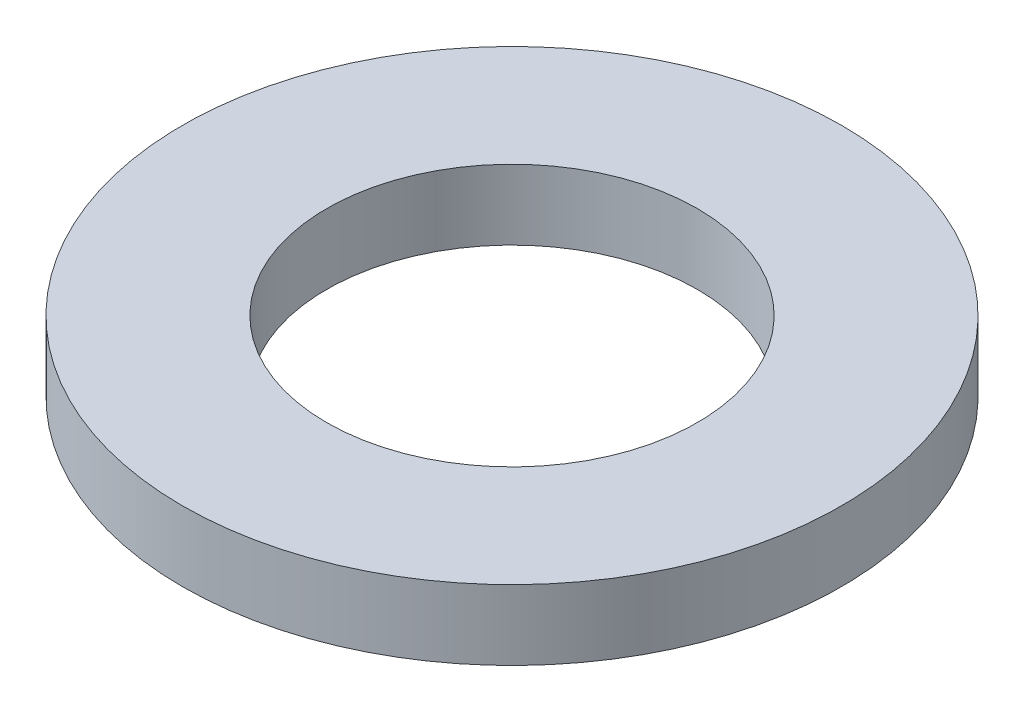
SolidWorks part; units mm, degrees
ref_plane "Front Plane" through (0, 0, 0) normal (0, 0, 1) x (1, 0, 0)
ref_plane "Top Plane" through (0, 0, 0) normal (0, 1, 0) x (1, 0, 0)
ref_plane "Right Plane" through (0, 0, 0) normal (1, 0, 0) x (0, 0, -1)
sketch "Sketch1" plane through (0, 0, 0) normal (0, 1, 0) x (1, 0, 0)
  circle A0 centre (0, 0) radius 80
  dimension "FLANGE_OD" = 160
extrude "Boss-Extrude1" add sketch "Sketch1" along normal blind 17
sketch "Sketch2" plane through (0, 0, 0) normal (0, 1, 0) x (1, 0, 0)
  circle A0 centre (0, 0) radius 45
  dimension "BORE_D" = 90
extrude "Cut-Extrude1" cut sketch "Sketch2" along normal through all
sketch "Sketch3" plane through (0, 17, 0) normal (0, 1, 0) x (1, 0, 0)
  circle A0 centre (0, 0) radius 26.8071 construction
  circle A1 centre (-26.8071, 0) radius 5.8758
  dimension "BOLT_D" = 11.7515
  dimension "BOLT_PCD" = 53.6142
extrude "Cut-Extrude2" cut sketch "Sketch3" against normal blind 12.1453 rebuild error yes
pattern_circular "CirPattern1" count 4 over 360 rebuild error yes
